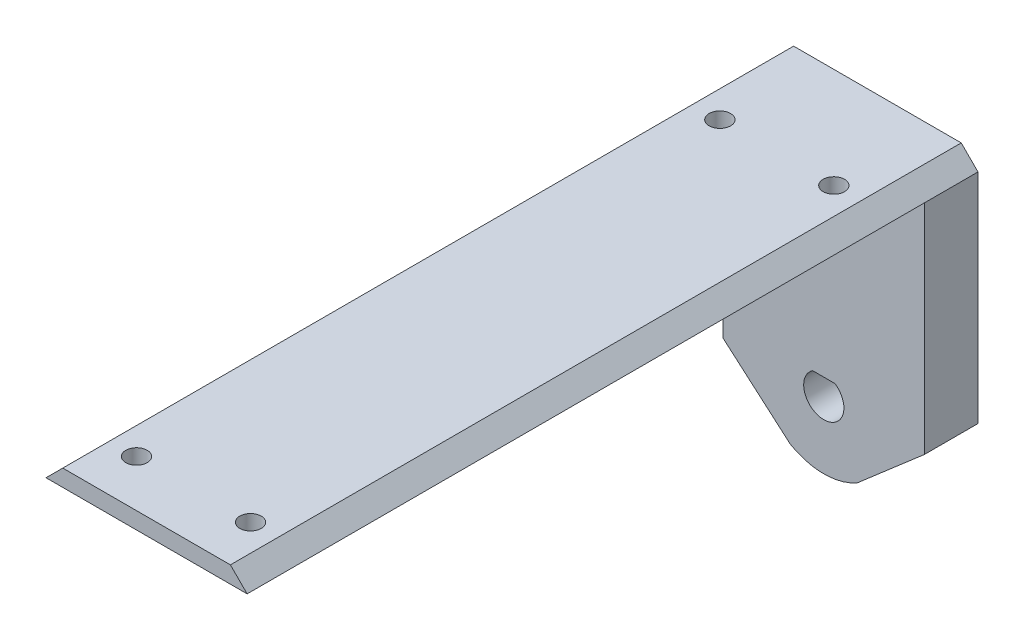
SolidWorks part; units mm, degrees
note: The reader was unsure of these and kept them because the rebuilt part matched: shared geometry of "Sketch1<5>".
material "ABS"
ref_plane "Front Plane" through (0, 0, 0) normal (0, 0, 1) x (1, 0, 0)
ref_plane "Top Plane" through (0, 0, 0) normal (0, 1, 0) x (1, 0, 0)
ref_plane "Right Plane" through (0, 0, 0) normal (1, 0, 0) x (0, 0, -1)
sketch "Sketch1" plane through (0, 0, 0) normal (0, 0, 1) x (1, 0, 0)
  line L0 (0, 0) -> (0, -7) construction
  line L1 (5, -15.6603) -> (-5, -15.6603) construction
  line L2 (15, 25.5) -> (-15, 25.5)
  line L3 (15, -7) -> (-15, -7) construction
  line L4 (15, -7) -> (15, 25.5)
  line L5 (-15, -7) -> (-15, 25.5)
  line L6 (15, -7) -> (5, -15.6603)
  line L7 (-5, -15.6603) -> (-15, -7)
  line L8 (15, 25.5) -> (15, 28) construction
  line L9 (15, 28) -> (-15, 28) construction
  line L10 (-15, 28) -> (-15, 25.5) construction
  line L11 (-15, 25.5) -> (-12.5, 28)
  line L12 (15, 25.5) -> (12.5, 28)
  line L13 (-12.5, 28) -> (12.5, 28)
  line L14 (1.6583, -4.5) -> (-1.6583, -4.5)
  circle A1 centre (0, -7) radius 10 construction
  arc A2 (-1.6583, -4.5) -> (1.6583, -4.5) centre (0, -7) ccw
  arc A3 (5, -15.6603) -> (-5, -15.6603) centre (0, -7) cw
  point P1 (0, -7)
  point P6 (0, -15.6603)
  dimension "D1" = 30
  dimension "D3" = 20
  dimension "D4" = 6
  dimension "D5" = 10
  dimension "D2" = 7
  dimension "D6" = 32.5
  dimension "D7" = 2.5
  dimension "D8" = 45
  dimension "D9" = 45
  dimension "D10" = 2.5
extrude "Boss-Extrude1" add sketch "Sketch1" along normal blind 8
extrude "Boss-Extrude3" add sketch "Sketch1<5>" along normal blind 109 contours L13 L11 L2 L12
sketch "Sketch1<5>" plane through (0, 0, 0) normal (0, 0, 1) x (1, 0, 0) same geometry as "Sketch1"
hole_wizard "M3 Clearance Slot1" positions "Sketch5" profile "Sketch4" size "M3" standard "ANSI Metric" slot yes end condition through all
sketch "Sketch5" plane through (0, 28, 0) normal (0, 1, 0) x (1, 0, 0)
  line L4 (-8.5, 0) -> (-8.5, -109) construction
  line L5 (-12.5, 0) -> (12.5, 0) construction
  line L6 (-12.5, -109) -> (12.5, -109) construction
  line L8 (-12.5, -109) -> (-12.5, 0) construction
  line L9 (8.5, 0) -> (8.5, -109) construction
  line L11 (12.5, -109) -> (12.5, 0) construction
  line L12 (-12.5, -102) -> (12.5, -102) construction
  line L14 (-12.5, -15) -> (12.5, -15) construction
  point P0 (-8.5, -15)
  point P4 (8.5, -15)
  point P6 (-8.5, -102)
  point P8 (8.5, -102)
  dimension "D1" = 4
  dimension "D2" = 4
  dimension "D3" = 7
  dimension "D4" = 15
sketch "Sketch4" plane through (-8.5, 28, 15) normal (1, 0, 0) x (0, 0, 1)
  line L0 (0, 0) -> (0, 45)
  line L1 (0, 45) -> (1.6, 45)
  line L2 (1.6, 45) -> (1.6, 0)
  line L5 (1.6, 0) -> (0, 0)
  line L11 (0, -6.35) -> (0, 107.95) construction
  dimension "Thru Hole Dia." = 3.2
  dimension "Thru Hole Depth" = 45
